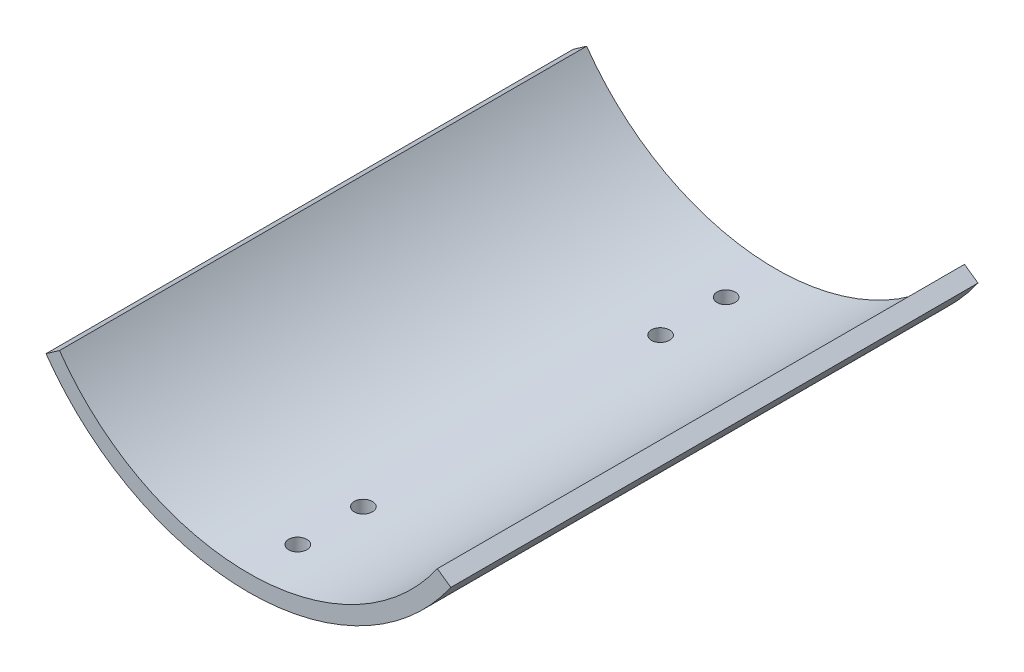
SolidWorks part; units mm, degrees
ref_plane "Front Plane" through (0, 0, 0) normal (0, 0, 1) x (1, 0, 0)
ref_plane "Top Plane" through (0, 0, 0) normal (0, 1, 0) x (1, 0, 0)
ref_plane "Right Plane" through (0, 0, 0) normal (1, 0, 0) x (0, 0, -1)
sketch "Sketch1" plane through (0, 0, 0) normal (0, 0, 1) x (1, 0, 0)
  line L0 (0, 0) -> (47.625, 0)
  line L3 (-36.4113, -25.4955) -> (-39.0121, -27.3166)
  line L4 (39.0121, -27.3166) -> (36.4113, -25.4955)
  circle A0 centre (0, 0) radius 44.45
  circle A2 centre (0, 0) radius 47.625
extrude "Boss-Extrude1" add sketch "Sketch1" along normal blind 50.8 and the other way blind 50.8 contours L3 A2 L4 A0 region at (0, -45.261, 0)
sketch "Sketch3" plane through (0, 0, 0) normal (0, 1, 0) x (1, 0, 0)
  circle A0 centre (0, 41.275) radius 1.7526
  circle A1 centre (0, 28.6363) radius 1.7526
  circle A2 centre (0, -28.6363) radius 1.7526
  circle A3 centre (0, -41.275) radius 1.7526
extrude "Cut-Extrude1" cut sketch "Sketch3" against normal blind 96
